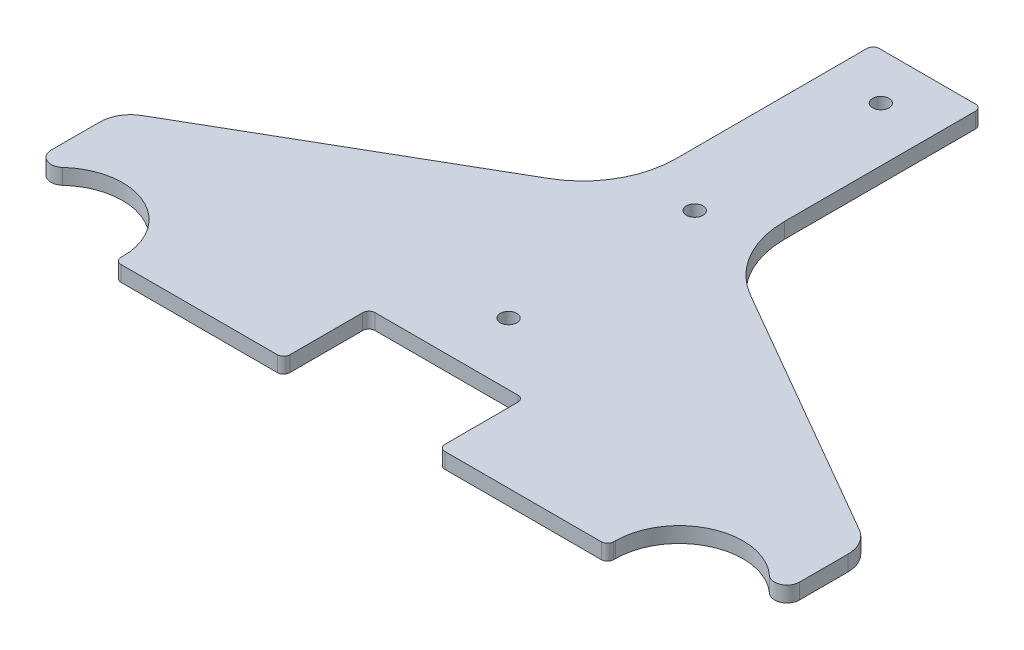
SolidWorks part; units mm, degrees
material "PC High Viscosity"
ref_plane "Front Plane" through (0, 0, 0) normal (0, 0, 1) x (1, 0, 0)
ref_plane "Top Plane" through (0, 0, 0) normal (0, 1, 0) x (1, 0, 0)
ref_plane "Right Plane" through (0, 0, 0) normal (1, 0, 0) x (0, 0, -1)
sketch "Sketch1" plane through (0, 0, 0) normal (0, 1, 0) x (1, 0, 0)
  line L0 (0, 0) -> (0, 228.6) construction
  line L1 (22.225, 228.6) -> (-22.225, 228.6)
  line L2 (-22.225, 228.6) -> (22.225, 228.6) construction
  line L3 (-22.225, 228.6) -> (-22.225, 0) construction
  line L4 (-22.225, 0) -> (22.225, 0) construction
  line L5 (22.225, 228.6) -> (22.225, 0) construction
  line L6 (-22.225, 228.6) -> (-22.225, 190.5)
  line L7 (-35.7155, 161.4143) -> (-168.5081, 49.0579)
  line L8 (-191.262, 0) -> (-191.262, -3.175)
  line L9 (-191.262, -3.175) -> (-153.162, -3.175)
  line L10 (-153.162, -3.175) -> (-153.162, 0)
  line L11 (-100.838, 0) -> (-100.838, -3.175)
  line L12 (-100.838, -3.175) -> (100.838, -3.175)
  line L13 (22.225, 228.6) -> (22.225, 190.5)
  line L14 (35.7155, 161.4143) -> (168.5081, 49.0579)
  line L15 (191.262, 0) -> (191.262, -3.175)
  line L16 (191.262, -3.175) -> (153.162, -3.175)
  line L17 (153.162, -3.175) -> (153.162, 0)
  line L18 (100.838, 0) -> (100.838, -3.175)
  circle A0 centre (-127, 0) radius 25.4 construction
  circle A1 centre (127, 0) radius 25.4 construction
  arc A2 (-22.225, 190.5) -> (-35.7155, 161.4143) centre (-60.325, 190.5) cw
  arc A3 (-168.5081, 49.0579) -> (-191.262, 0) centre (-127, 0) ccw
  arc A4 (-153.162, 0) -> (-100.838, 0) centre (-127, 0) cw
  arc A5 (22.225, 190.5) -> (35.7155, 161.4143) centre (60.325, 190.5) ccw
  arc A6 (168.5081, 49.0579) -> (191.262, 0) centre (127, 0) cw
  arc A7 (153.162, 0) -> (100.838, 0) centre (127, 0) ccw
  point P35 (0, -3.175)
  dimension "D1" = 50.8
  dimension "D6" = 26.162
  dimension "D8" = 38.1
  dimension "D9" = 38.1
  dimension "D2" = 44.45
  dimension "D3" = 228.6
  dimension "D4" = 254
  dimension "D5" = 38.1
  dimension "D7" = 3.175
extrude "Boss-Extrude1" add sketch "Sketch1" along normal blind 6.35
sketch "Sketch2" plane through (0, 6.35, 0) normal (0, 1, 0) x (1, 0, 0)
  line L0 (-31.75, -3.175) -> (-31.75, 31.75)
  line L1 (-100.838, -3.175) -> (100.838, -3.175) construction
  line L2 (-31.75, 31.75) -> (31.75, 31.75)
  line L3 (31.75, 31.75) -> (31.75, -3.175)
  line L4 (0, 31.75) -> (0, 0) construction
  line L5 (31.75, -3.175) -> (-31.75, -3.175)
  dimension "D1" = 31.75
  dimension "D2" = 63.5
extrude "Cut-Extrude1" cut sketch "Sketch2" against normal through all
hole_wizard "1/4 Clearance Hole1" positions "Sketch3" profile "Sketch4" hole size "1/4" standard "ANSI Inch" end condition through all
sketch "Sketch3" plane through (0, 6.35, 0) normal (0, 1, 0) x (1, 0, 0)
  line L0 (0, 228.6) -> (0, 31.75) construction
  line L1 (22.225, 228.6) -> (-22.225, 228.6) construction
  line L2 (31.75, 31.75) -> (-31.75, 31.75) construction
  point P0 (0, 209.55)
  point P2 (0, 133.35)
  point P4 (0, 57.15)
  dimension "D1" = 57.15
  dimension "D2" = 76.2
  dimension "D3" = 76.2
sketch "Sketch4" plane through (0, 6.35, -209.55) normal (1, 0, 0) x (0, 0, 1)
  line L0 (0, 0) -> (0, 6.35)
  line L1 (0, 6.35) -> (3.3782, 6.35)
  line L2 (3.3782, 6.35) -> (3.3782, 0)
  line L5 (3.3782, 0) -> (0, 0)
  line L11 (0, -6.35) -> (0, 107.95) construction
  dimension "Thru Hole Dia." = 6.7564
  dimension "Thru Hole Depth" = 6.35
sketch "Sketch5" plane through (0, 6.35, 0) normal (0, 1, 0) x (1, 0, 0)
  line L0 (-153.162, -3.175) -> (-153.162, 62.0423)
  line L1 (-35.7155, 161.4143) -> (-168.5081, 49.0579) construction
  line L2 (-153.162, 62.0423) -> (-168.5081, 49.0579)
  line L3 (-191.262, -3.175) -> (-153.162, -3.175) construction
  line L4 (-191.262, 0) -> (-191.262, -3.175) construction
  line L5 (-191.262, -3.175) -> (-153.162, -3.175)
  line L6 (-191.262, 0) -> (-191.262, -3.175)
  line L7 (0, 228.6) -> (0, 31.75) construction
  line L8 (22.225, 228.6) -> (-22.225, 228.6) construction
  line L9 (31.75, 31.75) -> (-31.75, 31.75) construction
  line L10 (191.262, 0) -> (191.262, -3.175)
  line L11 (191.262, -3.175) -> (153.162, -3.175)
  line L12 (153.162, 62.0423) -> (168.5081, 49.0579)
  line L13 (153.162, -3.175) -> (153.162, 62.0423)
  arc A0 (-168.5081, 49.0579) -> (-191.262, 0) centre (-127, 0) ccw construction
  arc A1 (-168.5081, 49.0579) -> (-191.262, 0) centre (-127, 0) ccw
  arc A2 (168.5081, 49.0579) -> (191.262, 0) centre (127, 0) cw
extrude "Cut-Extrude2" cut sketch "Sketch5" against normal through all
fillet "Fillet1" radius 25.4 2 edges at (153.162, 3.175, -62.0423) (-153.162, 3.175, -62.0423)
fillet "Fillet2" radius 5.08 2 edges at (153.162, 3.175, 0) (-153.162, 3.175, 0)
fillet "Fillet3" radius 2.54 8 edges at (100.838, 3.175, 3.175) (-100.838, 3.175, 3.175) (22.225, 3.175, -228.6) (-22.225, 3.175, -228.6) (31.75, 3.175, 3.175) (31.75, 3.175, -31.75) (-31.75, 3.175, -31.75) (-31.75, 3.175, 3.175)
sketch "Sketch6" plane through (0, 6.35, 0) normal (0, 1, 0) x (1, 0, 0)
  line L1 (0, 0) -> (0, 228.6) construction
  line L2 (0, 228.6) -> (-197.9734, 342.9) construction
  line L3 (0, 0) -> (-197.9734, 342.9) construction
  line L6 (-22.225, 190.5) -> (-22.225, 172.8286)
  line L8 (19.685, 228.6) -> (-19.685, 228.6) construction
  line L9 (-134.2716, 25.1311) -> (-22.225, 89.8213)
  line L10 (-22.225, 31.75) -> (-22.225, 228.6) construction
  line L11 (29.21, 31.75) -> (-29.21, 31.75) construction
  line L12 (-22.225, 89.8213) -> (-22.225, 172.8286)
  line L13 (-35.7155, 161.4143) -> (-144.1684, 69.6519) construction
  line L15 (-153.162, 23.0567) -> (-153.162, 50.2614) construction
  line L16 (-153.162, 23.0567) -> (-153.162, 50.2614)
  line L17 (153.162, 23.0567) -> (153.162, 50.2614)
  line L19 (22.225, 89.8213) -> (22.225, 172.8286)
  line L20 (134.2716, 25.1311) -> (22.225, 89.8213)
  line L21 (-35.7155, 161.4143) -> (-144.1684, 69.6519)
  line L22 (22.225, 190.5) -> (22.225, 172.8286)
  line L23 (35.7155, 161.4143) -> (144.1684, 69.6519)
  line L24 (-202.837, 22.2066) -> (-22.225, 126.483) construction
  circle A0 centre (-127, 0) radius 25.4 construction
  arc A1 (-100.838, 0) -> (-144.654, 19.3077) centre (-127, 0) ccw construction
  arc A2 (-35.7155, 161.4143) -> (-22.225, 190.5) centre (-60.325, 190.5) ccw construction
  arc A6 (-153.162, 23.0567) -> (-144.654, 19.3077) centre (-148.082, 23.0567) ccw construction
  arc A7 (-144.1684, 69.6519) -> (-153.162, 50.2614) centre (-127.762, 50.2614) ccw construction
  arc A8 (-153.162, 23.0567) -> (-144.654, 19.3077) centre (-148.082, 23.0567) ccw
  arc A9 (-144.1684, 69.6519) -> (-153.162, 50.2614) centre (-127.762, 50.2614) ccw
  arc A10 (-144.654, 19.3077) -> (-134.2716, 25.1311) centre (-127, 0) cw
  arc A11 (144.654, 19.3077) -> (134.2716, 25.1311) centre (127, 0) ccw
  arc A12 (153.162, 23.0567) -> (144.654, 19.3077) centre (148.082, 23.0567) cw
  arc A13 (144.1684, 69.6519) -> (153.162, 50.2614) centre (127.762, 50.2614) cw
  arc A14 (-35.7155, 161.4143) -> (-22.225, 190.5) centre (-60.325, 190.5) ccw
  arc A15 (35.7155, 161.4143) -> (22.225, 190.5) centre (60.325, 190.5) cw
  dimension "D1" = 50.8
  dimension "D2" = 120
  dimension "D3" = 22.225
  dimension "D4" = 31.75
sketch "Sketch7" plane through (0, 6.35, 0) normal (0, 1, 0) x (1, 0, 0)
  line L1 (-22.225, 125.8579) -> (-153.162, 50.2614)
  line L4 (-22.225, 89.8213) -> (-22.225, 172.8286) construction
  line L5 (-153.162, 23.0567) -> (-153.162, 50.2614) construction
  line L6 (-202.837, 22.2066) -> (-22.225, 126.483) construction
  line L7 (-22.225, 125.8579) -> (-22.225, 190.5)
  line L8 (-22.225, 190.5) -> (-153.162, 60.8563)
  line L9 (-153.162, 60.8563) -> (-153.162, 50.2614)
  line L10 (0, 228.6) -> (0, 0) construction
  line L11 (19.685, 228.6) -> (-19.685, 228.6) construction
  line L12 (153.162, 60.8563) -> (153.162, 50.2614)
  line L13 (22.225, 190.5) -> (153.162, 60.8563)
  line L14 (22.225, 125.8579) -> (22.225, 190.5)
  line L15 (22.225, 125.8579) -> (153.162, 50.2614)
  arc A1 (-144.1684, 69.6519) -> (-153.162, 50.2614) centre (-127.762, 50.2614) ccw construction
extrude "Cut-Extrude4" cut sketch "Sketch7" against normal through all
fillet "Fillet5" radius 12.7 2 edges at (153.162, 3.175, -50.2614) (-153.162, 3.175, -50.2614)
fillet "Fillet6" radius 38.1 2 edges at (22.225, 3.175, -125.8579) (-22.225, 3.175, -125.8579)
equation "\"D3@Sketch3\"=\"D2@Sketch3\""
